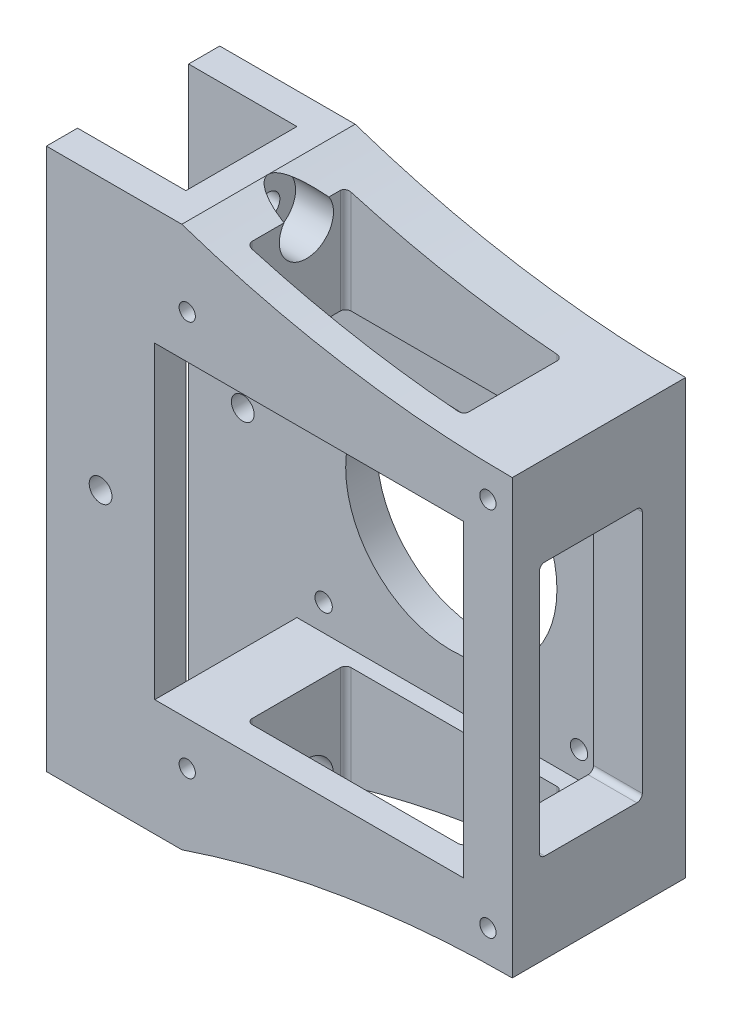
SolidWorks part; units mm, degrees
material "PBT Общее назначение"
ref_plane "Спереди" through (0, 0, 0) normal (0, 0, 1) x (1, 0, 0)
ref_plane "Сверху" through (0, 0, 0) normal (0, 1, 0) x (1, 0, 0)
ref_plane "Справа" through (0, 0, 0) normal (1, 0, 0) x (0, 0, -1)
sketch "Эскиз1" plane through (0, 0, 0) normal (0, 0, 1) x (1, 0, 0)
  line L0 (0, -50) -> (0, 50)
  line L1 (0, 50) -> (25, 50)
  line L2 (0, -50) -> (25, -50)
  line L3 (86, 40) -> (0, 40) construction
  line L4 (86, 40) -> (86, -40)
  line L5 (0, 0) -> (86, 0) construction
  arc A0 (25, 50) -> (86, 40) centre (86, 231.05) ccw
  arc A1 (25, -50) -> (86, -40) centre (86, -231.05) cw
  dimension "D1" = 50
  dimension "D2" = 86
  dimension "D3" = 25
  dimension "D4" = 40
  dimension "D5" = 61
extrude "Бобышка-Вытянуть1" add sketch "Эскиз1" along normal blind 52
sketch "Эскиз2" plane through (0, 0, 52) normal (0, 0, 1) x (1, 0, 0)
  line L0 (86, 0) -> (-10.2579, 0) construction
  line L1 (86, -40) -> (86, 40) construction
  line L2 (77, 28.5) -> (77, -28.5)
  line L3 (77, 28.5) -> (20, 28.5)
  line L4 (77, -28.5) -> (20, -28.5)
  line L5 (20, 28.5) -> (20, -28.5)
  line L6 (86, 0) -> (20, 0) construction
  line L7 (0, 50) -> (0, -50) construction
  dimension "D1" = 57
  dimension "D2" = 20
  dimension "D3" = 57
extrude "Вырез-Вытянуть1" cut sketch "Эскиз2" against normal through all
sketch "Эскиз3" plane through (0, 0, 0) normal (-1, 0, 0) x (0, 0, 1)
  line L0 (26, 50) -> (26, -50) construction
  line L1 (52, 50) -> (0, 50) construction
  line L2 (52, -50) -> (0, -50) construction
  line L3 (15.75, 50) -> (36.25, 50)
  line L4 (15.75, 50) -> (15.75, -50)
  line L5 (36.25, 50) -> (36.25, -50)
  line L6 (15.75, -50) -> (36.25, -50)
  line L7 (26, -50) -> (26, 50) construction
  dimension "D1" = 20.5
extrude "Вырез-Вытянуть2" cut sketch "Эскиз3" against normal blind 20
sketch "Эскиз4" plane through (0, 0, 0) normal (0, 0, -1) x (-1, 0, 0)
  line L4 (0, 50) -> (-25, 50)
  line L5 (-86, 40) -> (-86, -40)
  line L6 (-25, -50) -> (0, -50)
  line L7 (0, -50) -> (0, 50)
  line L8 (0, 50) -> (-25, 50)
  line L9 (-86, 40) -> (-86, -40)
  line L10 (-25, -50) -> (0, -50)
  line L11 (0, -50) -> (0, 50)
  arc A2 (-86, 40) -> (-25, 50) centre (-86, 231.05) ccw
  arc A3 (-25, -50) -> (-86, -40) centre (-86, -231.05) ccw
  arc A4 (-86, 40) -> (-25, 50) centre (-86, 231.05) ccw
  arc A5 (-25, -50) -> (-86, -40) centre (-86, -231.05) ccw
  dimension "D1" = 0
extrude "Вырез-Вытянуть3" cut sketch "Эскиз4" against normal blind 10
sketch "Эскиз5" plane through (0, 0, 52) normal (0, 0, 1) x (1, 0, 0)
  line L4 (25, 50) -> (0, 50)
  line L5 (0, 50) -> (0, -50)
  line L6 (0, -50) -> (25, -50)
  line L7 (86, -40) -> (86, 40)
  line L8 (25, 50) -> (0, 50)
  line L9 (0, 50) -> (0, -50)
  line L10 (0, -50) -> (25, -50)
  line L11 (86, -40) -> (86, 40)
  arc A2 (86, -40) -> (25, -50) centre (86, -231.05) ccw
  arc A3 (25, 50) -> (86, 40) centre (86, 231.05) ccw
  arc A4 (86, -40) -> (25, -50) centre (86, -231.05) ccw
  arc A5 (25, 50) -> (86, 40) centre (86, 231.05) ccw
  dimension "D1" = 0
extrude "Вырез-Вытянуть4" cut sketch "Эскиз5" against normal blind 10
sketch "Эскиз6" plane through (0, 0, 10) normal (0, 0, -1) x (-1, 0, 0)
  line L0 (-20, -28.5) -> (-77, -28.5) construction
  line L1 (-20, 28.5) -> (-20, -28.5) construction
  line L2 (-77, 28.5) -> (-20, 28.5) construction
  line L3 (-77, -28.5) -> (-77, 28.5) construction
  line L4 (-20, -28.5) -> (-77, -28.5)
  line L5 (-20, 28.5) -> (-20, -28.5)
  line L6 (-77, 28.5) -> (-20, 28.5)
  line L7 (-77, -28.5) -> (-77, 28.5)
extrude "Бобышка-Вытянуть2" add sketch "Эскиз6" against normal up to surface (5.75 mm away) up to face at (13.3333, 0, 15.75)
sketch "Эскиз7" plane through (0, 0, 15.75) normal (0, 0, 1) x (1, 0, 0)
  line L0 (20, -28.5) -> (20, 28.5) construction
  line L1 (77, -28.5) -> (20, -28.5) construction
  line L2 (77, 28.5) -> (77, -28.5) construction
  line L3 (20, 28.5) -> (77, 28.5) construction
  line L4 (20, -28.5) -> (20, 28.5) construction
  line L5 (77, -28.5) -> (20, -28.5) construction
  line L6 (77, 28.5) -> (77, -28.5) construction
  line L7 (20, 28.5) -> (77, 28.5) construction
  line L8 (48.5, -28.5) -> (48.5, 28.5) construction
  line L9 (20, 0) -> (77, 0) construction
  circle A0 centre (48.5, 0) radius 19.5
  dimension "D1" = 39
extrude "Вырез-Вытянуть5" cut sketch "Эскиз7" against normal through all
sketch "Эскиз8" plane through (20, 0, 0) normal (-1, 0, 0) x (0, 0, 1)
  line L0 (42, -40) -> (10, -40) construction
  line L1 (36.25, -40) -> (15.75, -40) construction
  line L2 (15.75, -50) -> (36.25, -50) construction
  line L3 (15.75, -50) -> (36.25, -50) construction
  line L4 (15.75, -28.5) -> (15.75, -50) construction
  line L5 (36.25, -50) -> (36.25, -28.5) construction
  line L6 (15.75, -40) -> (15.75, -50) construction
  line L7 (36.25, -50) -> (36.25, -40) construction
  line L8 (26, -50) -> (26, -40) construction
  line L9 (36.25, -45) -> (15.75, -45) construction
  line L10 (36.25, 50) -> (15.75, 50) construction
  line L12 (15.75, 50) -> (15.75, 28.5) construction
  line L13 (36.25, 28.5) -> (36.25, 50) construction
  line L14 (36.25, 50) -> (15.75, 50) construction
  line L15 (26, 40) -> (26, 50) construction
  line L16 (15.75, 50) -> (15.75, 40) construction
  line L17 (36.25, 40) -> (36.25, 50) construction
  line L18 (42, 40) -> (10, 40) construction
  line L19 (36.25, 40) -> (15.75, 40) construction
  line L20 (15.75, 45) -> (36.25, 45) construction
  circle A0 centre (26, -45) radius 2.1
  circle A1 centre (26, 45) radius 2.1
  dimension "D1" = 4.2
  dimension "D2" = 4.2
extrude "Вырез-Вытянуть6" cut sketch "Эскиз8" against normal through all
sketch "Эскиз9" plane through (0, 0, 10) normal (0, 0, -1) x (-1, 0, 0)
  line L0 (-86, 0) -> (0, 0) construction
  line L1 (-86, 40) -> (-86, -40) construction
  line L2 (0, -50) -> (0, 50) construction
ref_plane "СимY" through (0, 0, 0) normal (0, -1, 0) x (-1, 0, 0)
ref_plane "Плоскость2" through (25, 0, 0) normal (-1, 0, 0) x (0, 0, 1)
sketch "Эскиз10" plane through (25, 0, 0) normal (-1, 0, 0) x (0, 0, 1)
  circle A0 centre (26, 45) radius 2.1 construction
  circle A1 centre (26, -45) radius 2.1 construction
  circle A2 centre (26, 45) radius 2.1 construction
  circle A3 centre (26, -45) radius 2.1 construction
  circle A4 centre (26, 45) radius 5
  circle A5 centre (26, -45) radius 5
  dimension "D1" = 10
  dimension "D2" = 10
extrude "Вырез-Вытянуть7" cut sketch "Эскиз10" against normal through all
sketch "Эскиз12" plane through (0, 0, 10) normal (0, 0, -1) x (-1, 0, 0)
  line L0 (-20, 50) -> (0, 50) construction
  line L1 (0, 50) -> (0, -50) construction
  line L2 (-20, -50) -> (0, -50) construction
  line L3 (-20, 50) -> (0, 50) construction
  line L4 (0, 50) -> (0, -50) construction
  line L5 (-20, -50) -> (0, -50) construction
  line L6 (-20, 50) -> (-20, 28.5) construction
  line L7 (-20, 50) -> (-20, -50) construction
  line L8 (-20, 0) -> (0, 0) construction
  line L9 (-10, 50) -> (-10, -50) construction
  circle A0 centre (-10, 0) radius 2.1
  dimension "D1" = 4.2
extrude "Вырез-Вытянуть8" cut sketch "Эскиз12" against normal through all
sketch "Эскиз13" plane through (86, 0, 0) normal (1, 0, 0) x (0, 0, -1)
  line L0 (-42, 0) -> (-10, 0) construction
  line L1 (-42, -40) -> (-42, 40) construction
  line L2 (-26, 0) -> (-26, -36.6008) construction
  line L3 (-26, -40) -> (-10, -40) construction
ref_plane "СимZ" through (0, 0, 26) normal (0, 0, 1) x (0, -1, 0)
sketch "Эскиз14" plane through (0, 0, 10) normal (0, 0, -1) x (-1, 0, 0)
  line L0 (-48.5, 0) -> (-48.5, 19.5) construction
  line L1 (-48.5, 0) -> (-29, 0) construction
  line L2 (-72.07, 23.57) -> (-24.93, 23.57) construction
  line L3 (-72.07, 23.57) -> (-72.07, -23.57) construction
  line L4 (-24.93, 23.57) -> (-24.93, -23.57) construction
  line L5 (-72.07, -23.57) -> (-24.93, -23.57) construction
  line L6 (-48.5, 23.57) -> (-48.5, -23.57) construction
  line L7 (-24.93, 0) -> (-72.07, 0) construction
  circle A0 centre (-48.5, 0) radius 19.5 construction
  circle A1 centre (-48.5, 0) radius 19.5 construction
  circle A2 centre (-72.07, 23.57) radius 1.6
  circle A3 centre (-24.93, 23.57) radius 1.6
  circle A4 centre (-24.93, -23.57) radius 1.6
  circle A5 centre (-72.07, -23.57) radius 1.6
  dimension "D3" = 3.2
  dimension "D4" = 3.2
  dimension "D5" = 3.2
  dimension "D6" = 3.2
  dimension "D1" = 47.14
  dimension "D2" = 47.14
extrude "Вырез-Вытянуть9" cut sketch "Эскиз14" against normal up to surface (5.75 mm away) up to face at (10, 2.1, 15.75)
sketch "Эскиз15" plane through (86, 0, 0) normal (1, 0, 0) x (0, 0, -1)
  line L0 (-37, 23.5) -> (-18, 23.5)
  line L1 (-37, 23.5) -> (-37, -23.5)
  line L2 (-18, 23.5) -> (-18, -23.5)
  line L3 (-37, -23.5) -> (-18, -23.5)
  line L5 (-42, -40) -> (-42, 40) construction
  line L6 (-10, 40) -> (-10, -40) construction
  line L7 (-15.75, -28.5) -> (-42, -28.5) construction
  line L8 (-15.75, -28.5) -> (-42, -28.5) construction
  line L9 (-15.75, 28.5) -> (-42, 28.5) construction
  line L10 (-15.75, 28.5) -> (-42, 28.5) construction
  dimension "D1" = 5
  dimension "D2" = 8
  dimension "D3" = 5
  dimension "D4" = 5
  dimension "D5" = 5
extrude "Вырез-Вытянуть10" cut sketch "Эскиз15" against normal up to surface (9 mm away) up to face at (77, 0, 28.875)
sketch "Sketch1" plane through (0, 28.5, 0) normal (0, -1, 0) x (1, 0, 0)
  line L0 (72, 37) -> (72, 18.75)
  line L1 (72, 37) -> (32, 37)
  line L2 (72, 18.75) -> (32, 18.75)
  line L3 (32, 37) -> (32, 18.75)
  line L4 (77, 15.75) -> (77, 42) construction
  line L5 (20, 42) -> (77, 42) construction
  line L6 (77, 15.75) -> (20, 15.75) construction
  dimension "D1" = 5
  dimension "D2" = 40
  dimension "D3" = 5
  dimension "D4" = 3
extrude "Cut-Extrude1" cut sketch "Sketch1" against normal through all and the other way through all
fillet "Скругление1" radius 1 4 edges at (81.5, -23.5, 18) (81.5, -23.5, 37) (81.5, 23.5, 37) (81.5, 23.5, 18)
fillet "Скругление2" radius 1 4 edges at (32, 38.1452, 18.75) (72, 34.5068, 18.75) (72, 34.5068, 37) (32, 38.1452, 37)
fillet "Скругление3" radius 1 4 edges at (72, -34.5068, 37) (32, -38.1452, 37) (32, -38.1452, 18.75) (72, -34.5068, 18.75)
sketch "Эскиз16" plane through (0, 0, 42) normal (0, 0, 1) x (1, 0, 0)
  line L0 (72, 40.5136) -> (72, 28.5) construction
  line L1 (72, 40.5136) -> (72, 28.5)
  line L2 (20, 28.5) -> (77, 28.5) construction
  line L3 (72, 28.5) -> (86, 28.5)
  line L4 (86, -40) -> (86, 40) construction
  line L5 (86, 28.5) -> (86, 40)
  arc A0 (25, 50) -> (86, 40) centre (86, 231.05) ccw construction
  arc A1 (72, 40.5136) -> (86, 40) centre (86, 231.05) ccw
extrude "Бобышка-Вытянуть3" add sketch "Эскиз16" against normal up to surface (32 mm away) up to face at (70.47, -23.57, 10)
sketch "Эскиз17" plane through (0, 0, 42) normal (0, 0, 1) x (1, 0, 0)
  line L0 (86, -40) -> (86, 40) construction
  line L1 (86, -40) -> (86, -28.5)
  line L2 (77, -28.5) -> (20, -28.5) construction
  line L3 (86, -28.5) -> (72, -28.5)
  line L4 (72, -28.5) -> (72, -40.5136) construction
  line L5 (72, -28.5) -> (72, -40.5136)
  arc A0 (86, -40) -> (25, -50) centre (86, -231.05) ccw construction
  arc A1 (86, -40) -> (72, -40.5136) centre (86, -231.05) ccw
extrude "Бобышка-Вытянуть4" add sketch "Эскиз17" against normal up to surface (32 mm away) up to face at (36.8643, 0, 10)
sketch "Эскиз18" plane through (0, 0, 42) normal (0, 0, 1) x (1, 0, 0)
  line L0 (77, 28.5) -> (86, 28.5) construction
  line L1 (77, 28.5) -> (77, 40) construction
  line L2 (86, 28.5) -> (86, 40) construction
  line L3 (77, 40) -> (86, 40) construction
  line L4 (86, -40) -> (86, 40) construction
  line L5 (81.5, 40) -> (81.5, 28.5) construction
  line L6 (20, 28.5) -> (77, 28.5) construction
  line L7 (20, 28.5) -> (32, 28.5) construction
  line L8 (20, 28.5) -> (20, 50) construction
  line L9 (32, 28.5) -> (32, 50) construction
  line L10 (20, 50) -> (32, 50) construction
  line L11 (32, 28.5) -> (32, 47.7903) construction
  line L12 (32, 28.5) -> (32, 47.7903) construction
  line L13 (25, 50) -> (0, 50) construction
  line L14 (26, 28.5) -> (26, 50) construction
  line L15 (86, 0) -> (0, 0) construction
  line L16 (0, 50) -> (0, -50) construction
  line L17 (20, -28.5) -> (20, 28.5) construction
  line L18 (77, 28.5) -> (77, -28.5) construction
  line L19 (77, -28.5) -> (20, -28.5) construction
  line L20 (20, -28.5) -> (20, 28.5) construction
  line L21 (20, 28.5) -> (77, 28.5) construction
  line L22 (77, 28.5) -> (77, -28.5) construction
  line L23 (77, -28.5) -> (20, -28.5) construction
  line L24 (48.5, 28.5) -> (48.5, -28.5) construction
  line L26 (23.5, 25) -> (73.5, 25) construction
  line L27 (23.5, 25) -> (23.5, -25) construction
  line L28 (23.5, -25) -> (73.5, -25) construction
  line L29 (73.5, 25) -> (73.5, -25) construction
  line L30 (23.5, 25) -> (73.5, -25) construction
  line L31 (23.5, -25) -> (73.5, 25) construction
  circle A0 centre (81.5, 34.25) radius 1.5
  circle A1 centre (26, 36.5) radius 1.5
  circle A2 centre (81.5, -34.25) radius 1.5
  circle A3 centre (26, -36.5) radius 1.5
  point P38 (48.5, 0)
  dimension "D1" = 4.5
  dimension "D2" = 3
  dimension "D3" = 5.75
  dimension "D4" = 3
  dimension "D5" = 8
  dimension "D6" = 50
  dimension "D7" = 50
extrude "Вырез-Вытянуть11" cut sketch "Эскиз18" against normal blind 15
